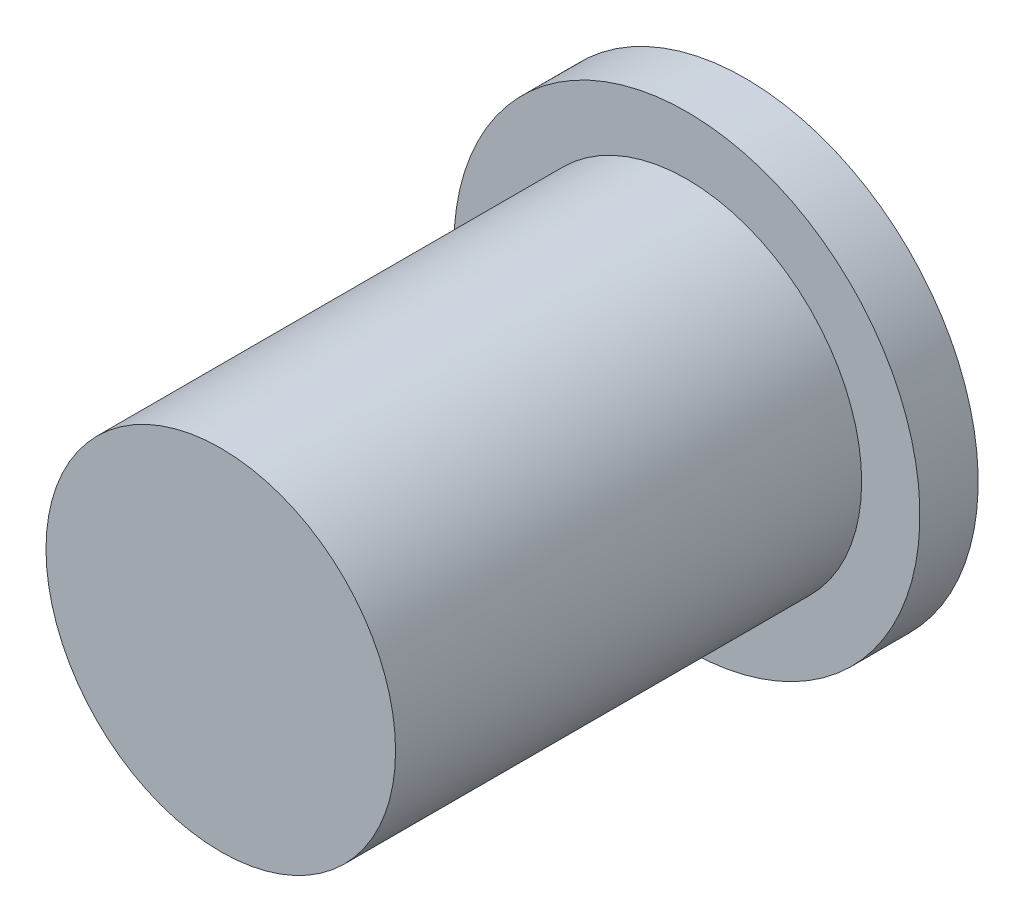
SolidWorks part; units mm, degrees
ref_plane "Front" through (0, 0, 0) normal (0, 0, 1) x (1, 0, 0)
ref_plane "Top" through (0, 0, 0) normal (0, 1, 0) x (1, 0, 0)
ref_plane "Sağ Düzlem" through (0, 0, 0) normal (1, 0, 0) x (0, 0, -1)
sketch "Sketch1" plane through (0, 0, 0) normal (0, 0, 1) x (1, 0, 0)
  circle A0 centre (0, 0) radius 15
extrude "Boss-Extrude1" add sketch "Sketch1" along normal blind 40
sketch "Sketch2" plane through (0, 0, 0) normal (0, 0, -1) x (-1, 0, 0)
  circle A0 centre (0, 0) radius 20
extrude "Boss-Extrude2" add sketch "Sketch2" along normal blind 5
